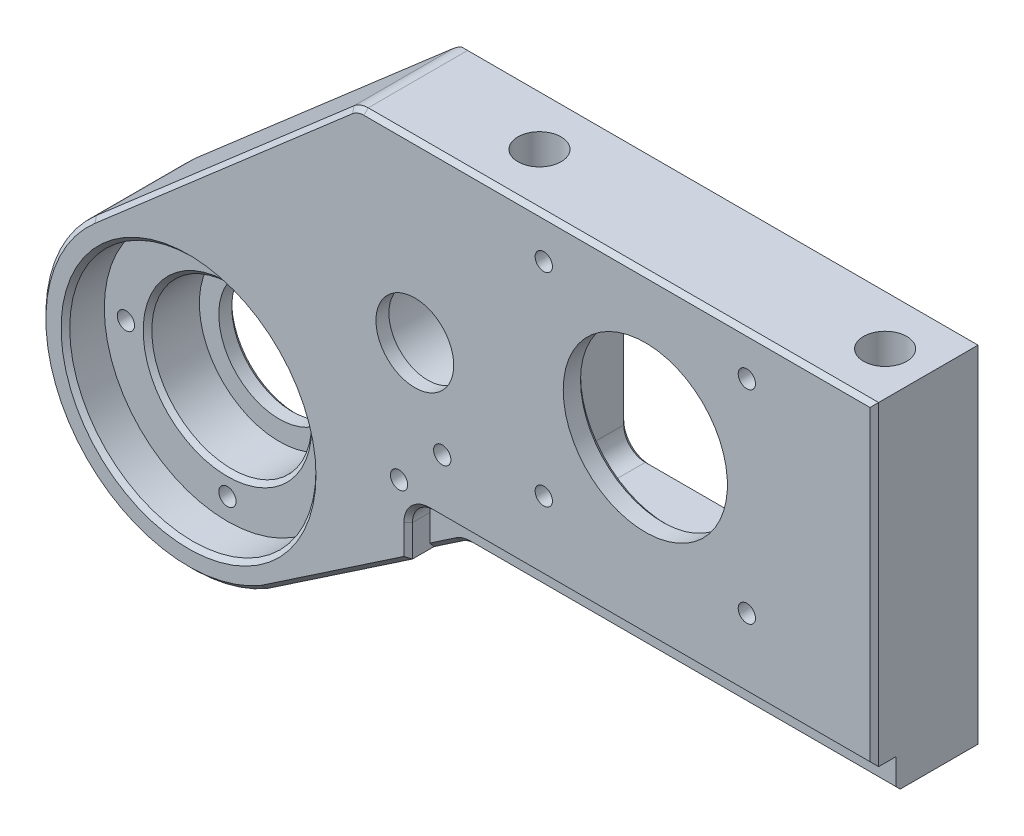
SolidWorks part; units mm, degrees
ref_plane "前视基准面" through (0, 0, 0) normal (0, 0, 1) x (1, 0, 0)
ref_plane "上视基准面" through (0, 0, 0) normal (0, 1, 0) x (1, 0, 0)
ref_plane "右视基准面" through (0, 0, 0) normal (1, 0, 0) x (0, 0, -1)
sketch "草图1" plane through (0, 0, 0) normal (0, 0, 1) x (1, 0, 0)
  line L0 (110.103, 97.6726) -> (10.103, 97.6726)
  line L2 (110.103, 17.6726) -> (130.103, 17.6726)
  line L3 (-11.3278, -10.3182) -> (30.103, 17.6726)
  line L4 (30.103, 17.6726) -> (110.103, 17.6726)
  line L5 (10.103, 97.6726) -> (-50.9269, 44.658)
  line L6 (130.103, 17.6726) -> (130.103, 97.6726)
  line L7 (130.103, 97.6726) -> (110.103, 97.6726)
  arc A0 (-50.9269, 44.658) -> (-11.3278, -10.3182) centre (-28.6187, 18.9769) ccw
  dimension "D1" = 80
  dimension "D2" = 100
  dimension "D3" = 80
  dimension "D4" = 50
  dimension "D5" = 20
extrude "拉伸1" add sketch "草图1" along normal blind 25
sketch "草图2" plane through (0, 0, 0) normal (0, 0, -1) x (-1, 0, 0)
  line L1 (-106.103, 93.6726) -> (-48.103, 93.6726)
  line L2 (-106.103, 93.6726) -> (-106.103, 35.6726)
  line L3 (-106.103, 35.6726) -> (-48.103, 35.6726)
  line L4 (-48.103, 93.6726) -> (-48.103, 35.6726)
  line L5 (-130.103, 97.6726) -> (-10.103, 97.6726) construction
  line L6 (-130.103, 17.6726) -> (-130.103, 97.6726) construction
  dimension "D1" = 58
  dimension "D2" = 58
  dimension "D3" = 24
  dimension "D4" = 4
extrude "切除-拉伸1" cut sketch "草图2" against normal blind 20
sketch "草图3" plane through (0, 0, 20) normal (0, 0, -1) x (-1, 0, 0)
  line L0 (-106.103, 35.6726) -> (-48.103, 35.6726) construction
  line L1 (-106.103, 93.6726) -> (-106.103, 35.6726) construction
  circle A0 centre (-77.103, 64.6726) radius 19
  point P4 (-106.103, 64.6726)
  dimension "D1" = 38
  dimension "D2" = 29
  dimension "D3" = 29
extrude "切除-拉伸2" cut sketch "草图3" against normal through all
hole_wizard "M4 螺纹孔1" positions "3D草图2" profile "草图5" tap size "M4" standard "ISO"
sketch3d "3D草图2"
  line L2 (100.603, 88.1726, 20) -> (53.603, 88.1726, 20)
  line L3 (100.603, 88.1726, 20) -> (100.603, 41.1726, 20)
  line L4 (100.603, 41.1726, 20) -> (53.603, 41.1726, 20)
  line L5 (53.603, 88.1726, 20) -> (53.603, 41.1726, 20)
  line L7 (77.103, 64.6726, 25) -> (77.103, 64.6726, 20) construction
  circle A0 centre (77.103, 64.6726, 20) radius 23.5
  point P204 (77.103, 64.6726, 43.5)
  point P208 (53.603, 88.1726, 20)
  point P213 (100.603, 88.1726, 20)
  point P215 (53.603, 88.1726, 20)
  point P217 (100.603, 41.1726, 20)
  point P219 (53.603, 41.1726, 20)
  point P226 (53.603, 88.1726, 20)
  dimension "D3" = 47
  dimension "D1" = 47
  dimension "D2" = 47
sketch "草图5" plane through (100.603, 88.1726, 20) normal (1, 0, 0) x (0, 1, 0)
  line L0 (0, 0) -> (0, 11.0914)
  line L1 (0, 11.0914) -> (1.65, 10.1)
  line L2 (1.65, 10.1) -> (1.65, 8)
  line L3 (1.65, 8) -> (2, 8)
  line L4 (2, 8) -> (2, 0)
  line L5 (2, 0) -> (0, 0)
  line L10 (0, 11.0914) -> (-1.65, 10.1) construction
  line L11 (0, -6.35) -> (0, 107.95) construction
  dimension "蹟恇謂郰芛眻噤" = 3.3
  dimension "蹟恇謂郰芛旮僅" = 10.1
  dimension "蹟恇翋眻噤" = 4
  dimension "蹟恇旮僅" = 8
  dimension "絳芛褒僅" = 118
sketch "草图6" plane through (0, 0, 25) normal (0, 0, 1) x (1, 0, 0)
  line L0 (30.103, 24.6726) -> (22.215, 24.6726)
  line L1 (130.103, 17.6726) -> (30.103, 17.6726)
  line L2 (130.103, 17.6726) -> (130.103, 24.6726)
  line L3 (130.103, 24.6726) -> (30.103, 24.6726)
  line L5 (22.215, 24.6726) -> (22.215, 12.3434)
  line L6 (-11.3278, -10.3182) -> (30.103, 17.6726) construction
  line L7 (22.215, 12.3434) -> (30.103, 17.6726)
  dimension "D1" = 7
extrude "切除-拉伸3" cut sketch "草图6" against normal blind 5
sketch "草图10" plane through (0, 0, 25) normal (0, 0, 1) x (1, 0, 0)
  circle A0 centre (-28.6187, 18.9769) radius 14
  dimension "D1" = 28
extrude "切除-拉伸7" cut sketch "草图10" against normal through all
sketch "草图11" plane through (0, 0, 25) normal (0, 0, 1) x (1, 0, 0)
  circle A0 centre (-28.6187, 18.9769) radius 18.5
  dimension "D1" = 37
extrude "切除-拉伸8" cut sketch "草图11" against normal blind 21
sketch "草图12" plane through (0, 0, 25) normal (0, 0, 1) x (1, 0, 0)
  circle A0 centre (-28.6187, 18.9769) radius 28.5
  dimension "D1" = 57
extrude "切除-拉伸9" cut sketch "草图12" against normal blind 9
hole_wizard "M10x1.25 螺纹孔1" positions "草图14" profile "草图13" tap size "M10x1.25" standard "ISO"
sketch "草图14" plane through (0, 17.6726, 0) normal (0, -1, 0) x (1, 0, 0)
  line L0 (130.103, 20) -> (130.103, 0) construction
  line L1 (30.103, 0) -> (130.103, 0) construction
  line L2 (30.103, 20) -> (30.103, 0) construction
  point P0 (120.103, 10)
  point P1 (40.103, 10)
  point P8 (30.103, 10)
  dimension "D1" = 10
  dimension "D2" = 10
  dimension "D3" = 10
  dimension "D4" = 10
sketch "草图13" plane through (120.103, 17.6726, 10) normal (1, 0, 0) x (0, 0, -1)
  line L0 (0, 0) -> (0, 36.3938)
  line L1 (0, 36.3938) -> (4.4, 33.75)
  line L2 (4.4, 33.75) -> (4.4, 30)
  line L3 (4.4, 30) -> (5, 30)
  line L4 (5, 30) -> (5, 0)
  line L5 (5, 0) -> (0, 0)
  line L10 (0, 36.3938) -> (-4.4, 33.75) construction
  line L11 (0, -6.35) -> (0, 107.95) construction
  dimension "蹟恇謂郰芛眻噤" = 8.8
  dimension "蹟恇謂郰芛旮僅" = 33.75
  dimension "蹟恇翋眻噤" = 10
  dimension "蹟恇旮僅" = 30
  dimension "絳芛褒僅" = 118
hole_wizard "M4 螺纹孔2" positions "草图16" profile "草图15" tap size "M4" standard "ISO"
sketch "草图16" plane through (0, 0, 16) normal (0, 0, 1) x (1, 0, 0)
  line L0 (-28.6187, -981.0231) -> (-28.6187, 49018.9769) construction
  line L1 (-1028.6187, 18.9769) -> (48971.3813, 18.9769) construction
  circle A0 centre (-28.6187, 18.9769) radius 23.5
  point P0 (-28.6187, 42.4769)
  point P1 (-52.1189, 18.9769)
  point P3 (-5.1187, 18.9769)
  point P5 (-52.1189, 18.9769)
  point P26 (-28.6187, -4.5231)
  dimension "D1" = 47
sketch "草图15" plane through (-28.6187, 42.4769, 16) normal (1, 0, 0) x (0, -1, 0)
  line L0 (0, 0) -> (0, 11.0914)
  line L1 (0, 11.0914) -> (1.65, 10.1)
  line L2 (1.65, 10.1) -> (1.65, 8)
  line L3 (1.65, 8) -> (2, 8)
  line L4 (2, 8) -> (2, 0)
  line L5 (2, 0) -> (0, 0)
  line L10 (0, 11.0914) -> (-1.65, 10.1) construction
  line L11 (0, -6.35) -> (0, 107.95) construction
  dimension "蹟恇謂郰芛眻噤" = 3.3
  dimension "蹟恇謂郰芛旮僅" = 10.1
  dimension "蹟恇翋眻噤" = 4
  dimension "蹟恇旮僅" = 8
  dimension "絳芛褒僅" = 118
hole_wizard "M10x1.25 螺纹孔2" positions "草图18" profile "草图17" tap size "M10x1.25" standard "ISO"
sketch "草图18" plane through (0, 97.6726, 0) normal (0, 1, 0) x (-1, 0, 0)
  line L0 (-130.103, 0) -> (-10.103, 0) construction
  line L1 (-130.103, 25) -> (-130.103, 0) construction
  point P0 (-40.103, 12.5)
  point P1 (-120.103, 12.5)
  dimension "D1" = 80
  dimension "D2" = 12.5
  dimension "D3" = 12.5
  dimension "D4" = 90
sketch "草图17" plane through (40.103, 97.6726, 12.5) normal (1, 0, 0) x (0, 0, 1)
  line L0 (0, 0) -> (0, 26.3938)
  line L1 (0, 26.3938) -> (4.4, 23.75)
  line L2 (4.4, 23.75) -> (4.4, 20)
  line L3 (4.4, 20) -> (5, 20)
  line L4 (5, 20) -> (5, 0)
  line L5 (5, 0) -> (0, 0)
  line L10 (0, 26.3938) -> (-4.4, 23.75) construction
  line L11 (0, -6.35) -> (0, 107.95) construction
  dimension "蹟恇謂郰芛眻噤" = 8.8
  dimension "蹟恇謂郰芛旮僅" = 23.75
  dimension "蹟恇翋眻噤" = 10
  dimension "蹟恇旮僅" = 20
  dimension "絳芛褒僅" = 118
hole_wizard "M4 螺纹孔3" positions "草图20" profile "草图19" tap size "M4" standard "ISO"
sketch "草图20" plane through (0, 0, 25) normal (0, 0, 1) x (1, 0, 0)
  line L0 (30.103, 17.6726) -> (130.103, 17.6726) construction
  line L1 (130.103, 24.6726) -> (130.103, 97.6726) construction
  point P0 (30.103, 37.6726)
  point P1 (20.103, 27.6726)
  dimension "D1" = 10
  dimension "D2" = 20
  dimension "D3" = 100
  dimension "D4" = 110
sketch "草图19" plane through (30.103, 37.6726, 25) normal (1, 0, 0) x (0, -1, 0)
  line L0 (0, 0) -> (0, 11.0914)
  line L1 (0, 11.0914) -> (1.65, 10.1)
  line L2 (1.65, 10.1) -> (1.65, 8)
  line L3 (1.65, 8) -> (2, 8)
  line L4 (2, 8) -> (2, 0)
  line L5 (2, 0) -> (0, 0)
  line L10 (0, 11.0914) -> (-1.65, 10.1) construction
  line L11 (0, -6.35) -> (0, 107.95) construction
  dimension "蹟恇謂郰芛眻噤" = 3.3
  dimension "蹟恇謂郰芛旮僅" = 10.1
  dimension "蹟恇翋眻噤" = 4
  dimension "蹟恇旮僅" = 8
  dimension "絳芛褒僅" = 118
fillet "圆角1" radius 5 1 edges at (48.103, 35.6726, 10)
fillet "圆角2" radius 5 3 edges at (48.103, 93.6726, 10) (106.103, 35.6726, 10) (106.103, 93.6726, 10)
fillet "圆角3" radius 5 1 edges at (22.215, 24.6726, 22.5)
chamfer "倒角1" distance 1 angle 45 1 edges at (58.103, 64.6726, 20)
chamfer "倒角2" distance 1 angle 45 16 edges at (-56.221, -0.9049, 0) (9.3876, 3.6772, 0) (80.103, 17.6726, 0) (130.103, 57.6726, 0) (70.103, 97.6726, 0) (-20.412, 71.1653, 0) (49.5675, 37.137, 0) (48.103, 64.6726, 0) (49.5675, 92.2081, 0) (77.103, 93.6726, 0) (104.6386, 92.2081, 0) (106.103, 64.6726, 0) (104.6386, 37.137, 0) (77.103, 35.6726, 0) (-14.6187, 18.9769, 0) (-10.1187, 18.9769, 16)
chamfer "倒角3" distance 1 angle 45 1 edges at (-0.1187, 18.9769, 25)
fillet "圆角5" radius 5 1 edges at (10.103, 97.6726, 13)
fillet "圆角7" radius 5 1 edges at (30.103, 17.6726, 10.5)
chamfer "倒角4" distance 1 angle 45 3 edges at (25.5248, 14.5795, 20) (30.1701, 17.4535, 20) (80.8684, 17.6726, 20)
chamfer "倒角5" distance 1 angle 45 1 edges at (130.103, 61.1726, 25)
chamfer "倒角6" distance 1 angle 45 3 edges at (22.215, 16.008, 25) (23.6795, 23.2081, 25) (78.159, 24.6726, 25)
chamfer "倒角7" distance 1 angle 45 2 edges at (-21.1172, 70.5526, 25) (70.5372, 97.6726, 25)
chamfer "倒角8" distance 1 angle 45 1 edges at (-53.607, -4.1047, 25)
sketch "草图23" plane through (0, 0, 25) normal (0, 0, 1) x (1, 0, 0)
  circle A0 centre (23.7574, 56.9615) radius 30 construction
  circle A1 centre (77.103, 64.6726) radius 53.9 construction
  circle A2 centre (-28.6187, 18.9769) radius 64.7 construction
  circle A3 centre (77.103, 64.6726) radius 10
  circle A4 centre (-28.6187, 18.9769) radius 30 construction
  dimension "D1" = 60
  dimension "D2" = 129.4
  dimension "D3" = 107.8
  dimension "D4" = 20
  dimension "D5" = 60
sketch "草图25" plane through (0, 0, 0) normal (0, 0, -1) x (-1, 0, 0)
  line L0 (735.7255, -688.1299) -> (-34619.6136, 34667.2092) construction
  line L1 (-723.8602, -676.9334) -> (34631.4789, 34678.4056) construction
  line L2 (734.9364, -678.1484) -> (-34620.4026, 34677.1906) construction
  line L3 (-700.9402, -676.0752) -> (34654.3989, 34679.2639) construction
  circle A0 centre (28.6187, 18.9769) radius 20 construction
  dimension "D1" = 40
  dimension "D2" = 40
  dimension "D3" = 15.6
  dimension "D4" = 6.5
hole_wizard "M3 螺纹孔1" positions "3D草图4" profile "草图26" tap size "M3" standard "ISO"
sketch3d "3D草图4"
  line L0 (-734.9364, -678.1484, 0) -> (34620.4026, 34677.1906, 0) construction
  line L1 (723.8602, -676.9334, 0) -> (-34631.4789, 34678.4056, 0) construction
  point P0 (-4.9306, 51.8574, 0)
sketch "草图26" plane through (-4.9306, 51.8574, 0) normal (1, 0, 0) x (0, 1, 0)
  line L0 (0, 0) -> (0, 8.2511)
  line L1 (0, 8.2511) -> (1.25, 7.5)
  line L2 (1.25, 7.5) -> (1.25, 6)
  line L3 (1.25, 6) -> (1.5, 6)
  line L4 (1.5, 6) -> (1.5, 0)
  line L5 (1.5, 0) -> (0, 0)
  line L10 (0, 8.2511) -> (-1.25, 7.5) construction
  line L11 (0, -6.35) -> (0, 107.95) construction
  dimension "蹟恇謂郰芛眻噤" = 2.5
  dimension "蹟恇謂郰芛旮僅" = 7.5
  dimension "蹟恇翋眻噤" = 3
  dimension "蹟恇旮僅" = 6
  dimension "絳芛褒僅" = 118
sketch "草图27" plane through (0, 0, 0) normal (0, 0, -1) x (-1, 0, 0)
  line L0 (142157.0817, -142109.4861) -> (-176040.9698, 176088.5654) construction
  line L1 (-142122.2964, -142097.4314) -> (176075.7551, 176100.6201) construction
  circle A0 centre (11.3653, 36.2303) radius 1.05
  dimension "D1" = 2.1
extrude "切除-拉伸10" cut sketch "草图27" against normal blind 5
sketch "草图28" plane through (0, 0, 25) normal (0, 0, 1) x (1, 0, 0)
  circle A0 centre (23.7574, 56.9615) radius 9
  dimension "D1" = 18
extrude "切除-拉伸11" cut sketch "草图28" against normal through all
sketch "草图30" plane through (0, 0, 0) normal (0, 0, -1) x (-1, 0, 0)
  circle A0 centre (-23.7574, 56.9615) radius 12.01
  dimension "D1" = 24.02
extrude "切除-拉伸12" cut sketch "草图30" against normal blind 22
sketch "草图31" plane through (0, 0, 0) normal (0, 0, -1) x (-1, 0, 0)
  line L0 (-23.7574, -943.0385) -> (-23.7574, 49056.9615) construction
  line L2 (-10.7574, 41.7629) -> (-10.7574, 72.1602)
  line L3 (-36.7574, 41.7629) -> (-36.7574, 72.1602)
  arc A0 (-10.7574, 72.1602) -> (-36.7574, 72.1602) centre (-23.7574, 56.9615) ccw
  arc A1 (-36.7574, 41.7629) -> (-10.7574, 41.7629) centre (-23.7574, 56.9615) ccw
  dimension "D1" = 40
  dimension "D2" = 13
  dimension "D3" = 13
extrude "切除-拉伸13" cut sketch "草图31" against normal blind 6
fillet "圆角8" radius 6 1 edges at (10.7574, 72.1602, 3)
fillet "圆角9" radius 6 1 edges at (36.7574, 72.1602, 3)
fillet "圆角10" radius 6 1 edges at (36.7574, 41.7629, 3)
fillet "圆角11" radius 6 1 edges at (10.7574, 41.7629, 3)
sketch "草图32" plane through (0, 0, 6) normal (0, 0, -1) x (-1, 0, 0)
  line L0 (-23.7574, -943.0385) -> (-23.7574, 49056.9615) construction
  line L1 (619.0302, -709.0829) -> (-31520.3503, 37593.1393) construction
  line L2 (-666.5451, -709.0829) -> (31472.8354, 37593.1393) construction
  circle A0 centre (-23.7574, 56.9615) radius 15 construction
  dimension "D1" = 30
  dimension "D2" = 40
  dimension "D3" = 40
hole_wizard "M3 螺纹孔2" positions "3D草图5" profile "草图33" tap size "M3" standard "ISO"
sketch3d "3D草图5"
  line L0 (666.5451, -709.0829, 6) -> (-31472.8354, 37593.1393, 6) construction
  line L1 (23.7574, -943.0385, 6) -> (23.7574, 49056.9615, 6) construction
  line L2 (-619.0302, -709.0829, 6) -> (31520.3503, 37593.1393, 6) construction
  circle A0 centre (23.7574, 56.9615, 6) radius 15 construction
  point P0 (14.1156, 68.4522, 6)
  point P4 (23.7574, 71.9615, 6)
  point P8 (33.3993, 68.4522, 6)
  point P12 (33.3993, 45.4709, 6)
  point P14 (23.7574, 41.9615, 6)
  point P16 (14.1156, 45.4709, 6)
  point P23 (23.7574, 56.9615, -9)
sketch "草图33" plane through (14.1156, 68.4522, 6) normal (1, 0, 0) x (0, 1, 0)
  line L0 (0, 0) -> (0, 8.2511)
  line L1 (0, 8.2511) -> (1.25, 7.5)
  line L2 (1.25, 7.5) -> (1.25, 6)
  line L3 (1.25, 6) -> (1.5, 6)
  line L4 (1.5, 6) -> (1.5, 0)
  line L5 (1.5, 0) -> (0, 0)
  line L10 (0, 8.2511) -> (-1.25, 7.5) construction
  line L11 (0, -6.35) -> (0, 107.95) construction
  dimension "蹟恇謂郰芛眻噤" = 2.5
  dimension "蹟恇謂郰芛旮僅" = 7.5
  dimension "蹟恇翋眻噤" = 3
  dimension "蹟恇旮僅" = 6
  dimension "絳芛褒僅" = 118
sketch "草图34" plane through (0, 0, 0) normal (0, 0, -1) x (-1, 0, 0)
  line L0 (-142145.2164, -142098.2897) -> (176052.8351, 176099.7619) construction
  line L1 (-48.2542, -1.3274) -> (62.745, -1.3274)
  line L2 (-48.2542, -1.3274) -> (-48.2542, -24.6852)
  line L3 (-48.2542, -24.6852) -> (62.745, -24.6852)
  line L4 (62.745, -1.3274) -> (62.745, -24.6852)
  line L5 (-130.103, 97.6726) -> (-11.9714, 97.6726) construction
  dimension "D1" = 99
extrude "切除-拉伸14" cut sketch "草图34" against normal blind 1
sketch "草图35" plane through (0, 0, 1) normal (0, 0, -1) x (-1, 0, 0)
  line L0 (28.6187, -981.0231) -> (28.6187, 49018.9769) construction
  line L1 (-972.896, -9.0231) -> (49027.104, -9.0231) construction
  dimension "D1" = 28
hole_wizard "M4 螺纹孔4" positions "3D草图6" profile "草图36" tap size "M4" standard "ISO"
sketch3d "3D草图6"
  line L0 (-28.6187, -981.0231, 1) -> (-28.6187, 49018.9769, 1) construction
  line L1 (972.896, -9.0231, 1) -> (-49027.104, -9.0231, 1) construction
  point P0 (-28.6187, -9.0231, 1)
sketch "草图36" plane through (-28.6187, -9.0231, 1) normal (1, 0, 0) x (0, 1, 0)
  line L0 (0, 0) -> (0, 11.0914)
  line L1 (0, 11.0914) -> (1.65, 10.1)
  line L2 (1.65, 10.1) -> (1.65, 8)
  line L3 (1.65, 8) -> (2, 8)
  line L4 (2, 8) -> (2, 0)
  line L5 (2, 0) -> (0, 0)
  line L10 (0, 11.0914) -> (-1.65, 10.1) construction
  line L11 (0, -6.35) -> (0, 107.95) construction
  dimension "蹟恇謂郰芛眻噤" = 3.3
  dimension "蹟恇謂郰芛旮僅" = 10.1
  dimension "蹟恇翋眻噤" = 4
  dimension "蹟恇旮僅" = 8
  dimension "絳芛褒僅" = 118
